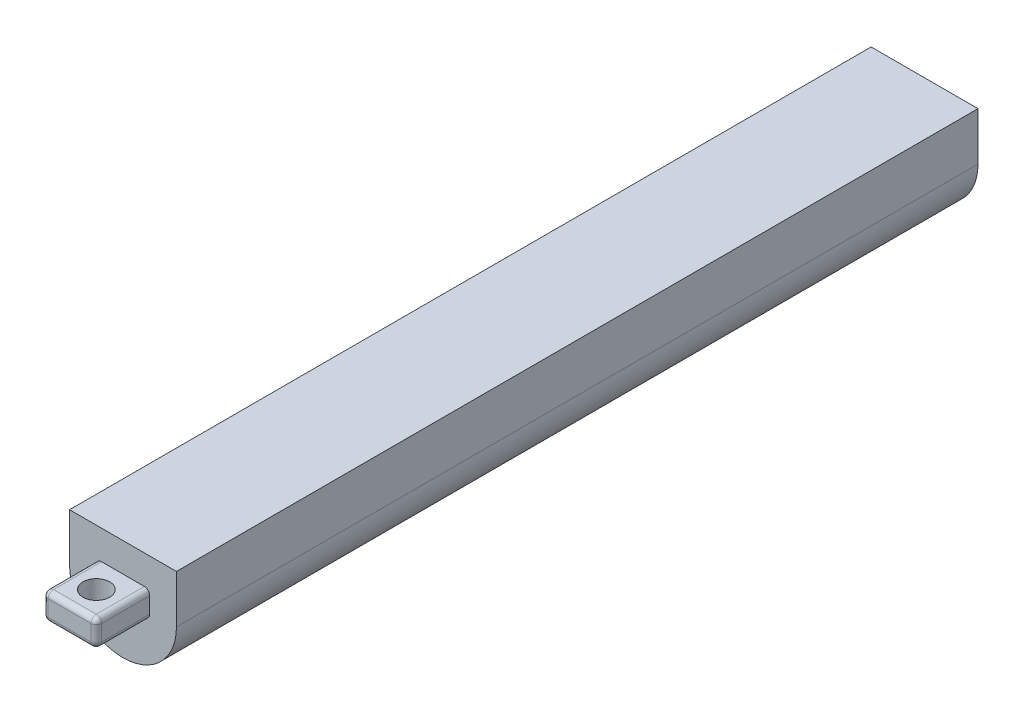
SolidWorks part; units mm, degrees
ref_plane "Front Plane" through (0, 0, 0) normal (0, 0, 1) x (1, 0, 0)
ref_plane "Top Plane" through (0, 0, 0) normal (0, 1, 0) x (1, 0, 0)
ref_plane "Right Plane" through (0, 0, 0) normal (1, 0, 0) x (0, 0, -1)
sketch "Sketch1" plane through (0, 0, 0) normal (0, 0, 1) x (1, 0, 0)
  line L1 (-20, 9) -> (20, 9)
  line L2 (-20, 9) -> (-20, -9)
  line L4 (20, 9) -> (20, -9)
  line L5 (-20, 9) -> (20, -9) construction
  line L6 (-20, -9) -> (20, 9) construction
  arc A0 (-20, -9) -> (20, -9) centre (0, -9) ccw
  point P0 (0, 0)
  dimension "D3" = 40
  dimension "D1" = 18
  dimension "D2" = 40
extrude "Boss-Extrude1" add sketch "Sketch1" along normal blind 500
sketch "Sketch2" plane through (0, 0, 500) normal (0, 0, 1) x (1, 0, 0)
  line L0 (0, 9) -> (0, -29) construction
  line L1 (20, 9) -> (-20, 9) construction
  line L3 (-10, -1.8737) -> (10, -1.8737)
  line L4 (-10, -1.8737) -> (-10, -11.8737)
  line L5 (-10, -11.8737) -> (10, -11.8737)
  line L6 (10, -1.8737) -> (10, -11.8737)
  line L7 (-10, -1.8737) -> (10, -11.8737) construction
  line L8 (-10, -11.8737) -> (10, -1.8737) construction
  arc A0 (-20, -9) -> (20, -9) centre (0, -9) ccw construction
  point P7 (0, -6.8737)
  dimension "D1" = 20
  dimension "D2" = 10
extrude "Boss-Extrude2" add sketch "Sketch2" along normal blind 20
sketch "Sketch3" plane through (0, -11.8737, 0) normal (0, -1, 0) x (1, 0, 0)
  line L0 (-10, 520) -> (10, 520) construction
  circle A0 centre (0, 510) radius 5
  dimension "D1" = 10
extrude "Cut-Extrude1" cut sketch "Sketch3" against normal blind 20
fillet "Fillet1" radius 2 1 edges at (0, -11.8737, 520)
fillet "Fillet2" radius 2 8 edges at (10, -5.8737, 520) (10, -11.8737, 509) (-10, -5.8737, 520) (-10, -11.288, 519.4142) (10, -11.288, 519.4142) (10, -1.8737, 510) (-10, -1.8737, 510) (-10, -11.8737, 509)
fillet "Fillet3" radius 2 3 edges at (9.4142, -2.4595, 519.4142) (-9.4142, -2.4595, 519.4142) (0, -1.8737, 520)
sketch "Sketch4" plane through (0, 0, 0) normal (0, 0, -1) x (-1, 0, 0)
  line L1 (-54.3935, 25.1568) -> (61.3887, 25.1568)
  line L2 (-54.3935, 25.1568) -> (-54.3935, -40.815)
  line L3 (-54.3935, -40.815) -> (61.3887, -40.815)
  line L4 (61.3887, 25.1568) -> (61.3887, -40.815)
extrude "Cut-Extrude2" cut sketch "Sketch4" against normal blind 200
